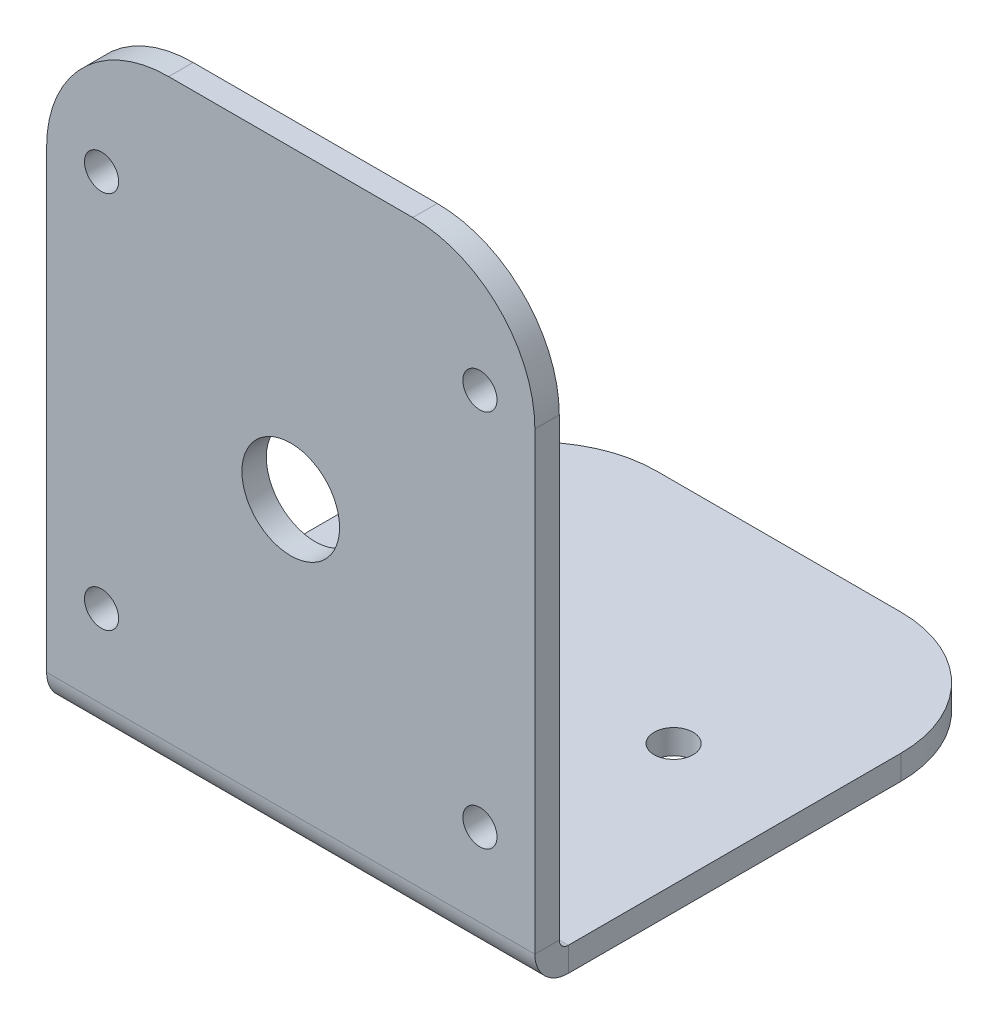
SolidWorks part; units mm, degrees
note: The reader was unsure of these and kept them because the rebuilt part matched: flange length of "Edge-Flange1".
ref_plane "Front Plane" through (0, 0, 0) normal (0, 0, 1) x (1, 0, 0)
ref_plane "Top Plane" through (0, 0, 0) normal (0, 1, 0) x (1, 0, 0)
ref_plane "Right Plane" through (0, 0, 0) normal (1, 0, 0) x (0, 0, -1)
sketch "Sketch1" plane through (0, 0, 0) normal (0, 0, 1) x (1, 0, 0)
  line L1 (-20, 25) -> (20, 25)
  line L2 (-20, 25) -> (-20, -25)
  line L3 (-20, -25) -> (20, -25)
  line L4 (20, 25) -> (20, -25)
  line L5 (-20, 25) -> (20, -25) construction
  line L6 (-20, -25) -> (20, 25) construction
  point P0 (0, 0)
  dimension "D1" = 50
  dimension "D2" = 40
base flange "Base-Flange1" sketch "Sketch1" thickness 2 reverse thickness direction no parameters "D1"=0.7366
edge flange "Edge-Flange1" sketch "Sketch8" flange angle 90 flange length 40 flange position material inside bend radius 0.7366 thickness 2 relief rectangular parameters "D6"=10
sketch "Sketch8" plane through (0, -25, -2) normal (0, -1, 0) x (-1, 0, 0)
  line L2 (-20, 0) -> (-20, 38)
  line L3 (-20, 38) -> (20, 38)
  line L4 (20, 38) -> (20, 0)
  line L7 (20, 0) -> (-20, 0) construction
  line L8 (20, 0) -> (-20, 0)
bend "EdgeBend1" bend radius 0.7366 bend angle 90 parameters "D5"=1
sketch "Sketch9" plane through (0, 0, -2) normal (0, 0, -1) x (-1, 0, 0)
  line L1 (-15.5, 15.5) -> (15.5, 15.5) construction
  line L2 (-15.5, 15.5) -> (-15.5, -15.5) construction
  line L3 (-15.5, -15.5) -> (15.5, -15.5) construction
  line L4 (15.5, 15.5) -> (15.5, -15.5) construction
  line L5 (-15.5, 15.5) -> (15.5, -15.5) construction
  line L6 (-15.5, -15.5) -> (15.5, 15.5) construction
  circle A0 centre (-15.5, 15.5) radius 1.4
  circle A1 centre (15.5, 15.5) radius 1.4
  circle A2 centre (15.5, -15.5) radius 1.4
  circle A3 centre (-15.5, -15.5) radius 1.4
  circle A4 centre (0, 0) radius 4
  point P0 (0, 0)
  dimension "D3" = 2.8
  dimension "D4" = 8
  dimension "D1" = 31
  dimension "D2" = 31
extrude "Cut-Extrude1" cut sketch "Sketch9" against normal up to next normal cut yes
sketch "Sketch11" plane through (0, -25, 0) normal (0, -1, 0) x (1, 0, 0)
  line L0 (-20, -21.3683) -> (20, -21.3683) construction
  line L1 (-20, -2.7366) -> (-20, -40) construction
  line L2 (20, -40) -> (20, -2.7366) construction
  circle A0 centre (-10, -21.3683) radius 1.6
  circle A1 centre (10, -21.3683) radius 1.6
  point P10 (0, -21.3683)
  dimension "D1" = 3.2
  dimension "D2" = 10
  dimension "D3" = 20
extrude "Cut-Extrude2" cut sketch "Sketch11" against normal up to next normal cut yes
fillet "Fillet1" radius 10 4 edges at (-20, -24, -40) (20, -24, -40) (-20, 25, -1) (20, 25, -1)
sketch "Bend-Lines1" [suppressed] plane through (0, 0, 0) normal (0, 1, 0) x (1, 0, 0)
sketch "Bounding-Box1" [suppressed] plane through (0, 0, 0) normal (0, 1, 0) x (1, 0, 0)
sheet metal parameters "Sheet-Metal1" thickness 2 parameters "D1"=0.7366
flat pattern "Flat-Pattern1" [suppressed]
sketch "Bend-Lines2" plane through (0, 0, 0) normal (0, 1, 0) x (1, 0, 0)
sketch3d "Bounding-Box2" [suppressed]
  line L0 (20, 30, 0) -> (20, -30, 0) construction
  line L1 (-20, 30, 0) -> (-20, -30, 0) construction
  line L2 (20, 30, 0) -> (-20, 30, 0) construction
  line L3 (20, -30, 0) -> (-20, -30, 0) construction
sketch "Sketch9-1" [suppressed] plane through (0, 0, -2) normal (0, 0, -1) x (-1, 0, 0)
  line L1 (-15.5, 15.5) -> (15.5, 15.5)
  line L2 (-15.5, 15.5) -> (-15.5, -15.5)
  line L3 (-15.5, -15.5) -> (15.5, -15.5)
  line L4 (15.5, 15.5) -> (15.5, -15.5)
  line L5 (-15.5, 15.5) -> (15.5, -15.5) construction
  line L6 (-15.5, -15.5) -> (15.5, 15.5) construction
  point P0 (0, 0)
  dimension "D1" = 31
  dimension "D2" = 31
sheet metal parameters "Sheet-Metal2" thickness 2 parameters "D1"=0.7366
flat pattern "Flat-Pattern1"
sketch "Bend-Lines2" plane through (0, 0, 0) normal (0, 0, 1) x (1, 0, 0)
  line L0 (-20, -23.6273) -> (20, -23.6273) construction
  line L1 (-20, -23.6273) -> (20, -23.6273) construction
sketch3d "Bounding-Box2" [suppressed]
  line L0 (20, 25, 0) -> (20, -62.2546, 0) construction
  line L1 (-20, 25, 0) -> (-20, -62.2546, 0) construction
  line L2 (20, 25, 0) -> (-20, 25, 0) construction
  line L3 (20, -62.2546, 0) -> (-20, -62.2546, 0) construction
bend of the flat pattern "Flatten-<EdgeBend1>1"
sheet metal parameters "Sheet-Metal3" thickness 2 parameters "D1"=0.7366
flat pattern "Flat-Pattern1"
sketch "Bend-Lines2" plane through (0, 0, 0) normal (0, 0, 1) x (1, 0, 0)
  line L0 (-20, -23.6273) -> (20, -23.6273) construction
  line L1 (-20, -23.6273) -> (20, -23.6273) construction
sketch3d "Bounding-Box2" [suppressed]
  line L0 (20, 25, 0) -> (20, -62.2546, 0) construction
  line L1 (-20, 25, 0) -> (-20, -62.2546, 0) construction
  line L2 (20, 25, 0) -> (-20, 25, 0) construction
  line L3 (20, -62.2546, 0) -> (-20, -62.2546, 0) construction
bend of the flat pattern "Flatten-<EdgeBend1>1"
sheet metal parameters "Sheet-Metal4" thickness 2 parameters "D1"=0.7366
flat pattern "Flat-Pattern1"
sketch "Bend-Lines2" plane through (0, 0, 0) normal (0, 0, 1) x (1, 0, 0)
  line L0 (-20, -23.6273) -> (20, -23.6273) construction
  line L1 (-20, -23.6273) -> (20, -23.6273) construction
sketch3d "Bounding-Box2" [suppressed]
  line L0 (20, 25, 0) -> (20, -62.2546, 0) construction
  line L1 (-20, 25, 0) -> (-20, -62.2546, 0) construction
  line L2 (20, 25, 0) -> (-20, 25, 0) construction
  line L3 (20, -62.2546, 0) -> (-20, -62.2546, 0) construction
bend of the flat pattern "Flatten-<EdgeBend1>1"
